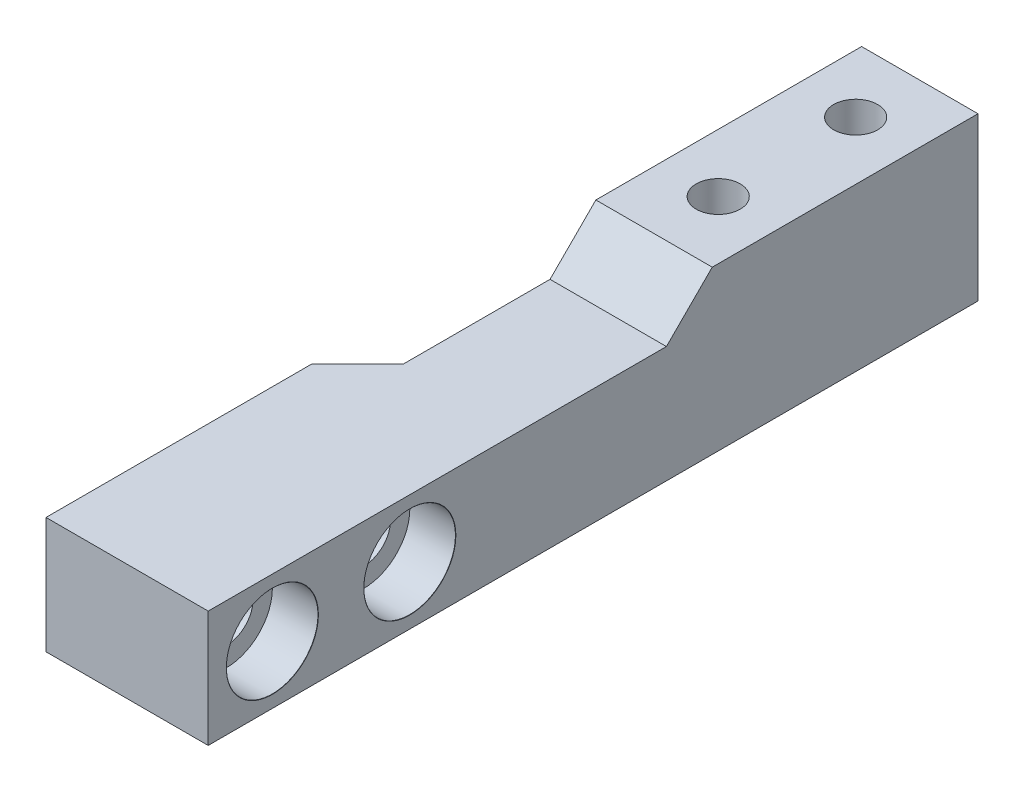
SolidWorks part; units mm, degrees
ref_plane "Front Plane" through (0, 0, 0) normal (0, 0, 1) x (1, 0, 0)
ref_plane "Top Plane" through (0, 0, 0) normal (0, 1, 0) x (1, 0, 0)
ref_plane "Right Plane" through (0, 0, 0) normal (1, 0, 0) x (0, 0, -1)
sketch "Sketch2" plane through (0, 0, 0) normal (0, 1, 0) x (1, 0, 0)
  line L1 (-6.35, -42) -> (6.35, -42)
  line L2 (-6.35, -42) -> (-6.35, 42)
  line L3 (-6.35, 42) -> (6.35, 42)
  line L4 (6.35, -42) -> (6.35, 42)
  line L5 (-6.35, -42) -> (6.35, 42) construction
  line L6 (-6.35, 42) -> (6.35, -42) construction
  point P0 (0, 0)
  dimension "D1" = 84
  dimension "D2" = 12.7
extrude "Boss-Extrude1" add sketch "Sketch2" along normal blind 12.7
sketch "Sketch5" plane through (0, 12.7, 0) normal (0, 1, 0) x (1, 0, 0)
  line L0 (6.35, 42) -> (-6.35, 42) construction
  line L2 (-6.35, 42) -> (6.35, 42)
  line L3 (-6.35, 42) -> (-6.35, 13)
  line L4 (-6.35, 13) -> (6.35, 13)
  line L5 (6.35, 42) -> (6.35, 13)
  point P7 (0, 13)
  dimension "D1" = 12.7
  dimension "D2" = 29
extrude "Boss-Extrude2" add sketch "Sketch5" along normal blind 5
hole_wizard "CBORE for M4 SHCS1" positions "Sketch3" profile "Sketch4" counterbore size "M4" standard "ANSI Metric" end condition through all
sketch "Sketch3" plane through (0, 0, 0) normal (0, -1, 0) x (-1, 0, 0)
  line L0 (0, 35) -> (0, 20) construction
  line L1 (0, -20) -> (0, -35) construction
  line L2 (0, 20) -> (0, -20) construction
  circle A0 centre (0, -20) radius 2.5 construction
  circle A1 centre (0, -35) radius 2.5 construction
  point P0 (0, 35)
  point P2 (0, 20)
  point P28 (0, 0)
  dimension "D2" = 5
  dimension "D1" = 15
  dimension "D3" = 15
  dimension "D4" = 40
sketch "Sketch4" plane through (0, 0, -35) normal (1, 0, 0) x (0, 0, -1)
  line L0 (0, 0) -> (0, 17.7)
  line L1 (0, 17.7) -> (2.4, 17.7)
  line L3 (2.4, 17.7) -> (2.4, 4)
  line L4 (4, 4) -> (2.4, 4)
  line L5 (4, 4) -> (4, 0.021)
  line L6 (4, 0.021) -> (4.025, 0)
  line L7 (4.025, 0) -> (0, 0)
  line L8 (-4, 0.021) -> (-4.025, 0) construction
  line L11 (0, -6.35) -> (0, 107.95) construction
  dimension "Thru Hole Dia." = 4.8
  dimension "Thru Hole Depth" = 17.7
  dimension "C'Bore Dia." = 8
  dimension "C'Bore Depth" = 4
  dimension "Near C'Sink Dia." = 8.05
  dimension "Near C'Sink Angle" = 100
sketch "Sketch8" plane through (-6.35, 0, 0) normal (-1, 0, 0) x (0, 0, 1)
  line L0 (-42, 0) -> (42, 0) construction
  line L1 (42, 12.7) -> (13, 12.7)
  line L2 (42, 12.7) -> (42, 0)
  line L3 (42, 0) -> (13, 0)
  line L4 (13, 12.7) -> (13, 0)
  dimension "D1" = 29
extrude "Boss-Extrude3" add sketch "Sketch8" along normal blind 5
hole_wizard "CBORE for M5 SHCS2" positions "Sketch6" profile "Sketch7" counterbore size "M5" standard "ANSI Metric" end condition through all
sketch "Sketch6" plane through (6.35, 0, 0) normal (1, 0, 0) x (0, 0, -1)
  line L0 (-35, 6.35) -> (-20, 6.35) construction
  line L2 (20, 6.35) -> (35, 6.35) construction
  line L4 (-20, 6.35) -> (20, 6.35) construction
  line L6 (-42, 12.7) -> (-42, 0) construction
  circle A0 centre (20, 6.35) radius 2.5 construction
  circle A1 centre (35, 6.35) radius 2.5 construction
  point P0 (-35, 6.35)
  point P2 (-20, 6.35)
  point P26 (0, 6.35)
  point P29 (-42, 6.35)
  dimension "D1" = 5
  dimension "D2" = 15
  dimension "D3" = 15
  dimension "D4" = 40
sketch "Sketch7" plane through (6.35, 6.35, 35) normal (0, 1, 0) x (0, 0, -1)
  line L0 (0, 0) -> (0, 17.7)
  line L1 (0, 17.7) -> (2.9, 17.7)
  line L3 (2.9, 17.7) -> (2.9, 5)
  line L4 (5, 5) -> (2.9, 5)
  line L5 (5, 5) -> (5, 0.021)
  line L6 (5, 0.021) -> (5.025, 0)
  line L7 (5.025, 0) -> (0, 0)
  line L8 (-5, 0.021) -> (-5.025, 0) construction
  line L11 (0, -6.35) -> (0, 107.95) construction
  dimension "Thru Hole Dia." = 5.8
  dimension "Thru Hole Depth" = 17.7
  dimension "C'Bore Dia." = 10
  dimension "C'Bore Depth" = 5
  dimension "Near C'Sink Dia." = 10.05
  dimension "Near C'Sink Angle" = 100
chamfer "Chamfer1" distance 5 angle 45 2 edges at (0, 12.7, -13) (-6.35, 6.35, 13)
